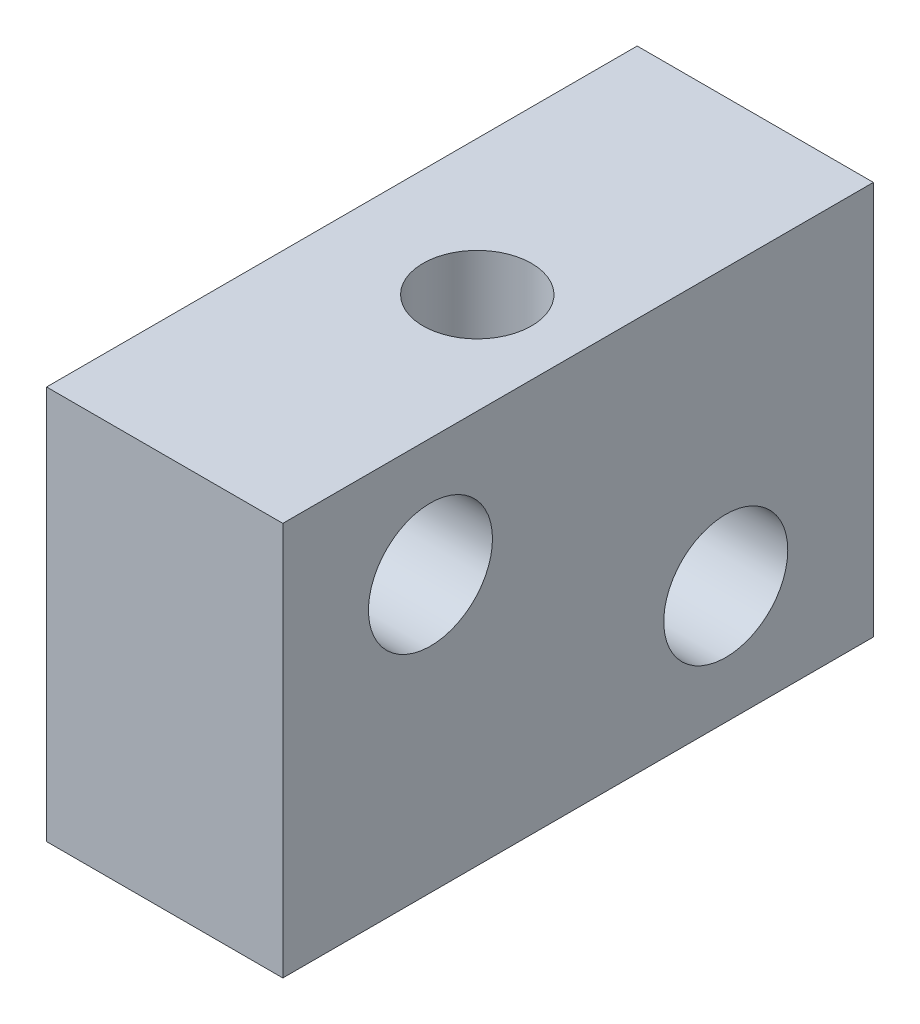
SolidWorks part; units mm, degrees
material "PET"
ref_plane "Front Plane" through (0, 0, 0) normal (1, 0, 0) x (0, 1, 0)
ref_plane "Top Plane" through (0, 0, 0) normal (0, 0, 1) x (0, 1, 0)
ref_plane "Right Plane" through (0, 0, 0) normal (0, 1, 0) x (-1, 0, 0)
sketch "Sketch1" plane through (0, 0, 0) normal (1, 0, 0) x (0, 1, 0)
  line L1 (6.35, -9.525) -> (-6.35, -9.525)
  line L2 (6.35, -9.525) -> (6.35, 9.525)
  line L3 (6.35, 9.525) -> (-6.35, 9.525)
  line L4 (-6.35, -9.525) -> (-6.35, 9.525)
  line L5 (6.35, -9.525) -> (-6.35, 9.525) construction
  line L6 (6.35, 9.525) -> (-6.35, -9.525) construction
  point P0 (0, 0)
  dimension "D1" = 19.05
  dimension "D2" = 12.7
extrude "Boss-Extrude1" add sketch "Sketch1" along normal blind 7.62
sketch "Sketch3" plane through (0, -6.35, 0) normal (0, -1, 0) x (1, 0, 0)
  line L10 (0, 9.525) -> (0, -9.525)
  line L11 (0, -9.525) -> (7.62, -9.525)
  line L12 (7.62, -9.525) -> (7.62, 9.525)
  line L13 (7.62, 9.525) -> (0, 9.525)
  line L14 (0, 9.525) -> (0, -9.525)
  line L15 (0, -9.525) -> (7.62, -9.525)
  line L16 (7.62, -9.525) -> (7.62, 9.525)
  line L17 (7.62, 9.525) -> (0, 9.525)
  circle A0 centre (4.3663, 0) radius 1.75
  circle A1 centre (4.3663, 0) radius 5 construction
  circle A2 centre (4.3663, 0) radius 3 construction
  point P2 (9.3663, 0)
  point P3 (2.6163, 0)
  point P6 (-6.35, 0)
  dimension "D1" = 3.5
  dimension "D2" = 10
  dimension "D6" = 6
  dimension "D3" = 15.7163
  dimension "D4" = 6.35
  dimension "D5" = 0
extrude "Cut-Extrude1" cut sketch "Sketch3" against normal blind 22.2885 contours A0 region at (4.3663, -6.35, 0)
sketch "Sketch4" plane through (7.62, 0, 0) normal (1, 0, 0) x (0, 1, 0)
  line L0 (-6.35, 9.525) -> (-6.35, -9.525) construction
  line L1 (2.54, -4.7625) -> (-2.54, -4.7625) construction
  line L2 (2.54, -4.7625) -> (2.54, 4.7625) construction
  line L3 (2.54, 4.7625) -> (-2.54, 4.7625) construction
  line L4 (-2.54, -4.7625) -> (-2.54, 4.7625) construction
  line L5 (2.54, -4.7625) -> (-2.54, 4.7625) construction
  line L6 (2.54, 4.7625) -> (-2.54, -4.7625) construction
  circle A3 centre (2.54, 4.7625) radius 2
  circle A4 centre (-2.54, -4.7625) radius 2
  circle A5 centre (2.54, 4.7625) radius 3.6 construction
  point P0 (0, 0)
  point P8 (2.54, 8.3625)
  point P14 (2.54, 6.7625)
  dimension "D3" = 4
  dimension "D4" = 1.6
  dimension "D1" = 3.81
  dimension "D2" = 9.525
extrude "Cut-Extrude2" cut sketch "Sketch4" against normal blind 22.2885 contours A4 | A3 region at (7.62, 2.54, 4.7625) region at (7.62, -2.54, -4.7625)
